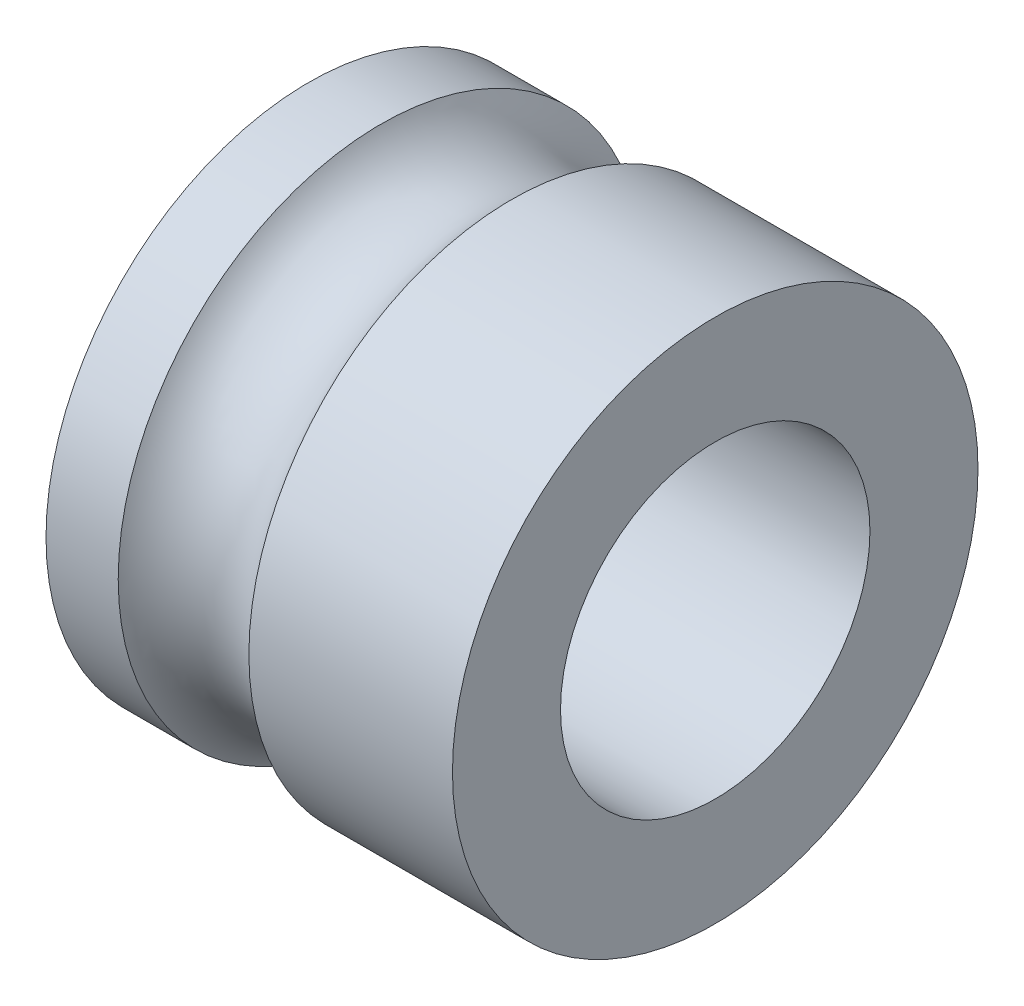
SolidWorks part; units mm, degrees
material "1060 Alloy"
ref_plane "Front Plane" through (0, 0, 0) normal (0, 0, 1) x (1, 0, 0)
ref_plane "Top Plane" through (0, 0, 0) normal (0, 1, 0) x (1, 0, 0)
ref_plane "Right Plane" through (0, 0, 0) normal (1, 0, 0) x (0, 0, -1)
sketch "Sketch1" plane through (0, 0, 0) normal (0, 0, 1) x (1, 0, 0)
  line L0 (0, 0) -> (4, 0)
  line L1 (0, 0) -> (-4, 0)
  line L2 (-4, 0) -> (-4, 3.142)
  line L3 (4, 0) -> (4, 3.142)
  line L4 (-4, 3.142) -> (-1.9, 3.142)
  line L5 (4, 3.142) -> (1.9, 3.142)
  line L6 (-1.9, 3.142) -> (1.9, 3.142) construction
  line L7 (-4, 3.142) -> (-4, -4.5) construction
  line L8 (-4, -4.5) -> (4, -4.5) construction
  arc A0 (-1.9, 3.142) -> (1.9, 3.142) centre (0, 4.2511) ccw
  dimension "D6" = 2.2
  dimension "D1" = 4
  dimension "D2" = 4
  dimension "D3" = 3.142
  dimension "D4" = 2.1
  dimension "D5" = 7.642
revolve "Revolve1" add sketch "Sketch1" angle 360 about L8
scale "Scale1" bodies to scale 101 scale about centroid uniform scaling yes scale factor 6
sketch "Sketch4" plane through (24, 0, 0) normal (1, 0, 0) x (0, 0, -1)
  circle A0 centre (0, -4.5) radius 45.852
extrude "Boss-Extrude1" add sketch "Sketch4" along normal blind 12.7
sketch "Sketch5" plane through (24, 0, 0) normal (-1, 0, 0) x (0, 0, 1)
  circle A0 centre (0, -4.5) radius 27
extrude "Cut-Extrude1" cut sketch "Sketch5" against normal through all
scale "Scale2" bodies to scale 104 scale about centroid uniform scaling yes scale factor 3.323882
sketch "Sketch7" plane through (105.4144, 0, 0) normal (1, 0, 0) x (0, 0, -1)
  circle A0 centre (0, -4.5) radius 89.7448 construction
  circle A1 centre (0, -4.5) radius 152.4066 construction
  circle A2 centre (0, -4.5) radius 89.7448
  circle A3 centre (0, -4.5) radius 152.4066
extrude "Boss-Extrude2" add sketch "Sketch7" along normal blind 33.99
scale "Scale3" [suppressed]
sketch "Sketch8" [suppressed] plane through (72.9418, 0, 0) normal (1, 0, 0) x (0, 0, -1)
  circle A0 centre (0, -4.5) radius 63.5007 construction
  circle A1 centre (0, -4.5) radius 63.5007
  circle A2 centre (0, -4.5) radius 76.2007
  dimension "D1" = 12.7
extrude "Boss-Extrude3" [suppressed] add sketch "Sketch8" along normal blind 12.7 from offset 31.75 contours A2 offset against normal yes
sketch "Sketch9" [suppressed] plane through (72.9418, 0, 0) normal (1, 0, 0) x (0, 0, -1)
  circle A0 centre (0, -4.5) radius 63.5007 construction
  circle A1 centre (0, -4.5) radius 63.5007
  circle A2 centre (0, -4.5) radius 37.3924 construction
  circle A3 centre (0, -4.5) radius 37.3924
extrude "Boss-Extrude4" [suppressed] add sketch "Sketch9" along normal blind 19.05
sketch "Sketch10" [suppressed] plane through (53.8918, 0, 0) normal (1, 0, 0) x (0, 0, -1)
  circle A0 centre (0, -4.5) radius 37.3924 construction
  circle A1 centre (0, -4.5) radius 37.3924
extrude "Cut-Extrude2" [suppressed] cut sketch "Sketch10" against normal through all
scale "Scale4" [suppressed]
sketch "Sketch11" [suppressed] plane through (75.6141, 0, 0) normal (1, 0, 0) x (0, 0, -1)
  circle A0 centre (0, -4.5) radius 44.7929 construction
  circle A1 centre (0, -4.5) radius 26.3763 construction
  circle A2 centre (0, -4.5) radius 44.7929
  circle A3 centre (0, -4.5) radius 26.3763
extrude "Boss-Extrude5" [suppressed] add sketch "Sketch11" along normal blind 41.32
scale "Scale5" [suppressed]
